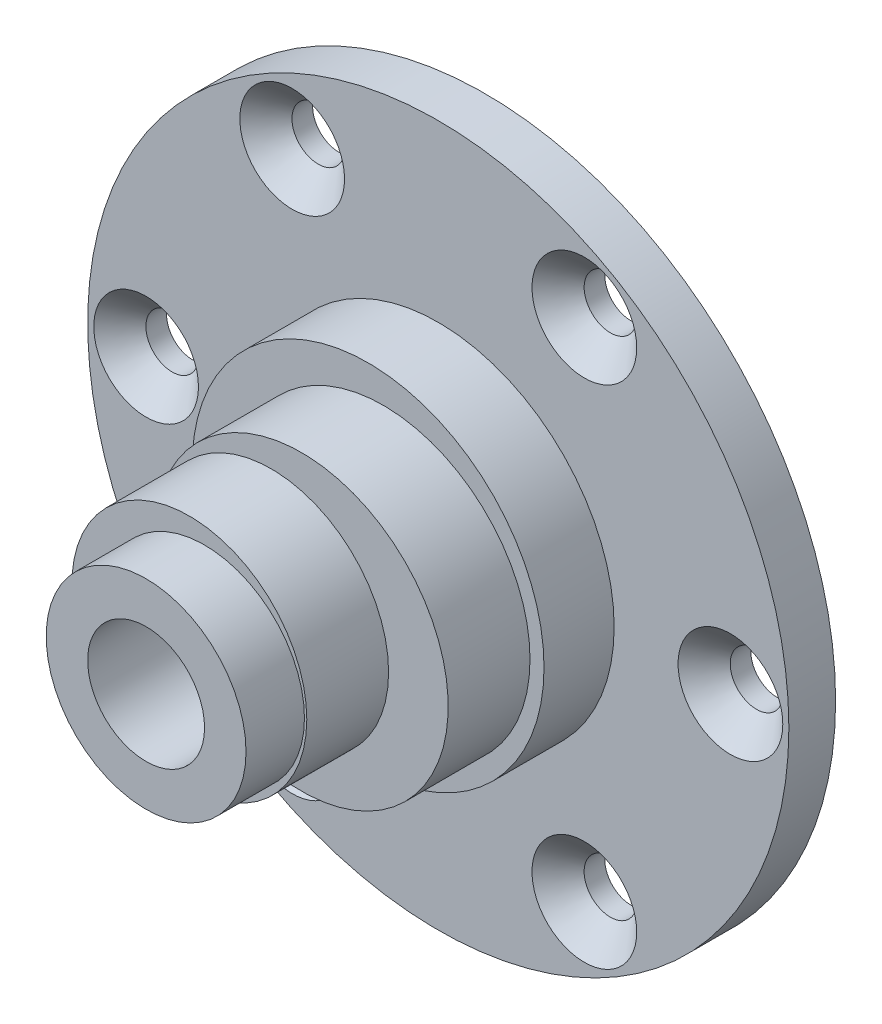
SolidWorks part; units mm, degrees
material "7075-T6, Plate (SS)"
ref_plane "Front Plane" through (0, 0, 0) normal (0, 0, 1) x (1, 0, 0)
ref_plane "Top Plane" through (0, 0, 0) normal (0, 1, 0) x (1, 0, 0)
ref_plane "Right Plane" through (0, 0, 0) normal (1, 0, 0) x (0, 0, -1)
sketch "Sketch1" plane through (0, 0, 0) normal (0, 0, 1) x (1, 0, 0)
  circle A0 centre (0, 0) radius 30 construction
  circle A1 centre (0, 0) radius 30
extrude "Boss-Extrude1" add sketch "Sketch1" along normal blind 4
sketch "Sketch2" plane through (0, 0, 4) normal (0, 0, 1) x (1, 0, 0)
  line L0 (0, 0) -> (0, 25) construction
  line L1 (0, 0) -> (-12.5, 21.6506) construction
  circle A0 centre (0, 0) radius 25 construction
  arc A3 (-44.5, 0) -> (44.5, 0) centre (0, 0) ccw
  arc A4 (44.5, 0) -> (-44.5, 0) centre (0, 0) ccw
  arc A5 (-44.5, 0) -> (44.5, 0) centre (0, 0) ccw
  arc A6 (44.5, 0) -> (-44.5, 0) centre (0, 0) ccw
  circle A11 centre (0, 0) radius 15.05
  circle A12 centre (0, 0) radius 10.05
  point P10 (-12.5, 21.6506)
  point P12 (12.5, 21.6506)
  point P13 (25, 0)
  point P14 (12.5, -21.6506)
  point P15 (-12.5, -21.6506)
  point P16 (-25, 0)
  point P17 (0, 0)
  point P22 (0, 0)
  dimension "D1" = 50
  dimension "D4" = 6
  dimension "D5" = 30.1
  dimension "D3" = 30
  dimension "D2" = 0
  dimension "D6" = 5
hole_wizard "CSK for M4 Hex Socket Countersunk Cap Screw1" positions "Sketch4" profile "Sketch3" countersink size "M4" standard "ISO" end condition through all
sketch "Sketch4" plane through (0, 0, 4) normal (0, 0, 1) x (1, 0, 0)
  point P4 (-12.5, 21.6506)
  point P7 (12.5, 21.6506)
  point P10 (25, 0)
  point P13 (-12.5, -21.6506)
  point P16 (12.5, -21.6506)
  point P19 (-25, 0)
sketch "Sketch3" plane through (-12.5, 21.6506, 4) normal (1, 0, 0) x (0, -1, 0)
  line L0 (0, 0) -> (0, 4)
  line L1 (0, 4) -> (2.25, 4)
  line L2 (2.25, 4) -> (2.25, 2.23)
  line L3 (2.25, 2.23) -> (4.48, 0)
  line L5 (4.48, 0) -> (0, 0)
  line L6 (-2.25, 2.23) -> (-4.48, 0) construction
  line L11 (0, -6.35) -> (0, 107.95) construction
  dimension "Thru Hole Dia." = 4.5
  dimension "Thru Hole Depth" = 4
  dimension "Near C'Sink Dia." = 8.96
  dimension "Near C'Sink Angle" = 90
extrude "Boss-Extrude3" add sketch "Sketch2" along normal blind 6 contours A11 A12 region at (-14.6243, 0, 4)
sketch "Sketch5" plane through (0, 0, 0) normal (0, 0, -1) x (-1, 0, 0)
  circle A0 centre (0, 0) radius 12
  dimension "D1" = 24
extrude "Cut-Extrude2" cut sketch "Sketch5" against normal blind 4
sketch "Sketch6" plane through (0, 0, 10) normal (0, 0, 1) x (1, 0, 0)
  circle A0 centre (1.3, 0) radius 12.55
  point P2 (0, 0)
  dimension "D1" = 25.1
  dimension "D2" = 1.3
extrude "Boss-Extrude4" add sketch "Sketch6" along normal blind 7
sketch "Sketch7" plane through (0, 0, 17) normal (0, 0, 1) x (1, 0, 0)
  circle A0 centre (-1.3, 0) radius 10.05
  point P2 (0, 0)
  dimension "D1" = 20.1
  dimension "D2" = 1.3
extrude "Boss-Extrude5" add sketch "Sketch7" along normal blind 7
sketch "Sketch8" plane through (0, 0, 24) normal (0, 0, 1) x (1, 0, 0)
  circle A0 centre (0, 0) radius 8.55
  dimension "D1" = 17.1
extrude "Boss-Extrude6" add sketch "Sketch8" along normal blind 5
sketch "Sketch9" plane through (0, 0, 29) normal (0, 0, 1) x (1, 0, 0)
  circle A0 centre (0, 0) radius 5
  dimension "D1" = 10
extrude "Cut-Extrude3" cut sketch "Sketch9" against normal blind 30
